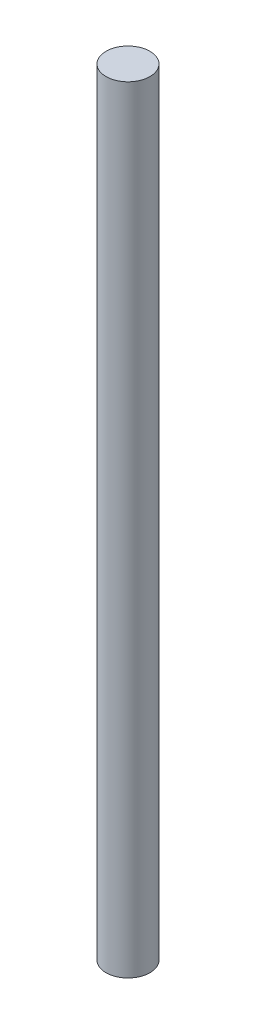
SolidWorks part; units mm, degrees
ref_plane "Front Plane" through (0, 0, 0) normal (0, 0, 1) x (1, 0, 0)
ref_plane "Top Plane" through (0, 0, 0) normal (0, 1, 0) x (1, 0, 0)
ref_plane "Right Plane" through (0, 0, 0) normal (1, 0, 0) x (0, 0, -1)
sketch "Sketch1" plane through (0, 0, 0) normal (0, 1, 0) x (1, 0, 0)
  circle A0 centre (0, 0) radius 5.0263
extrude "Boss-Extrude1" add sketch "Sketch1" along normal blind 177.8
